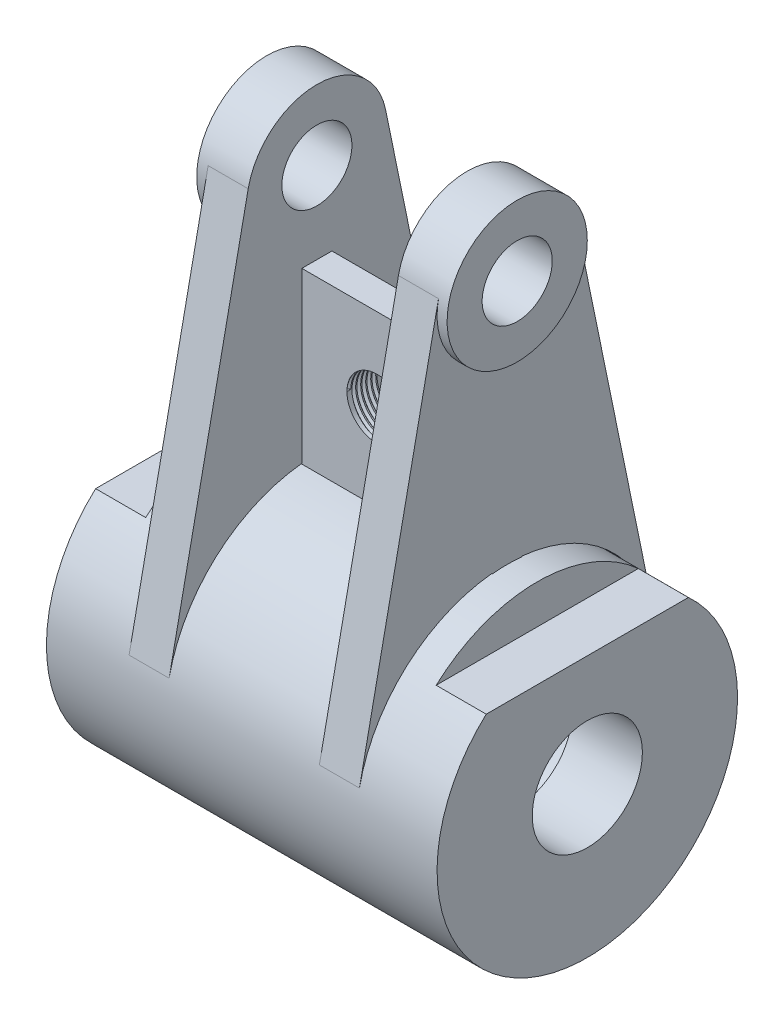
SolidWorks part; units mm, degrees
ref_plane "Front Plane" through (0, 0, 0) normal (0, 0, 1) x (1, 0, 0)
ref_plane "Top Plane" through (0, 0, 0) normal (0, 1, 0) x (1, 0, 0)
ref_plane "Right Plane" through (0, 0, 0) normal (1, 0, 0) x (0, 0, -1)
sketch "Sketch1" plane through (0, 0, 0) normal (1, 0, 0) x (0, 0, -1)
  circle A0 centre (0, 0) radius 30
  dimension "D1" = 60
extrude "Boss-Extrude1" add sketch "Sketch1" along normal mid plane 78
sketch "Sketch2" plane through (39, 0, 0) normal (1, 0, 0) x (0, 0, -1)
  line L0 (0, -30) -> (0, 22.1962)
  line L1 (-21.6282, 22.1962) -> (22.0652, 22.1962)
  circle A0 centre (0, 0) radius 30 construction
  circle A1 centre (0, 0) radius 30
  circle M3 centre (0, 0) radius 30
  dimension "D1" = 52.1962
extrude "Cut-Extrude1" cut sketch "Sketch2" against normal blind 10 contours L1 M3 region at (39, 25.3554, 0)
mirror "Mirror2" about plane through (0, 0, 0) normal (1, 0, 0) of "Cut-Extrude1"
sketch "Sketch3" plane through (0, 0, 0) normal (1, 0, 0) x (0, 0, -1)
  circle A0 centre (0, 0) radius 30
  circle A1 centre (0, 0) radius 18
  dimension "D1" = 36
extrude "Cut-Extrude2" cut sketch "Sketch3" against normal mid plane 50 contours A1
sketch "Sketch4" plane through (39, 0, 0) normal (1, 0, 0) x (0, 0, -1)
  circle A0 centre (0, 0) radius 11
  dimension "D1" = 22
extrude "Cut-Extrude3" cut sketch "Sketch4" against normal mid plane 188
sketch3d "3DSketch1" plane through (0, 0, 0) normal (0, 0, 1) x (1, 0, 0)
  dimension "D1" = 15
  dimension "D2" = 15
ref_plane "Plane3" through (15, 0, 0) normal (1, 0, 0) x (0, 0, -1)
ref_plane "Plane4" through (-15, 0, 0) normal (1, 0, 0) x (0, 0, -1)
sketch "Sketch6" plane through (-15, 0, 0) normal (1, 0, 0) x (0, 0, -1)
  line L0 (0, 0) -> (0, 80)
  line L1 (-13.7129, 82.8206) -> (-29.5004, 6.068)
  line L2 (13.7129, 82.8206) -> (29.5004, 6.068)
  line L3 (0, 80) -> (0, 63.7)
  line L4 (0, 63.7) -> (-3, 63.7)
  line L6 (-3, 63.7) -> (3, 63.7)
  line L7 (-3, 63.7) -> (-3, 26.2051)
  line L8 (-3, 26.2051) -> (3, 26.2051)
  line L9 (3, 63.7) -> (3, 26.2051)
  circle A0 centre (0, 0) radius 30.118
  circle A1 centre (0, 80) radius 7
  circle A2 centre (0, 80) radius 14
  dimension "D2" = 14
  dimension "D3" = 28
  dimension "D1" = 80
  dimension "D4" = 16.3
  dimension "D5" = 3
  dimension "D6" = 6
extrude "Boss-Extrude2" add sketch "Sketch6" against normal blind 10 contours A2 L0 L6 L9 A0 L2 | A2 L1 A0 L7 L4 L0 | A2 A1 | L7 L8 L9 L6 region at (-15, 45.6847, 13.1779) region at (-15, 45.6847, -13.1779) region at (-15, 71.404, 10.5441)
sketch "Sketch7" plane through (-25, 0, 0) normal (-1, 0, 0) x (0, 0, 1)
  line L4 (-3, 29.9682) -> (-3, 29.8496)
  line L5 (3, 29.8496) -> (3, 29.9682)
  line L6 (29.5004, 6.068) -> (13.7129, 82.8206)
  line L7 (-13.7129, 82.8206) -> (-29.5004, 6.068)
  line L8 (-3, 29.9682) -> (-3, 29.8496)
  line L9 (3, 29.8496) -> (3, 29.9682)
  line L10 (29.5004, 6.068) -> (13.7129, 82.8206)
  line L11 (-13.7129, 82.8206) -> (-29.5004, 6.068)
  circle A0 centre (0, 80) radius 14
  arc A5 (3, 29.8496) -> (-3, 29.8496) centre (0, 0) ccw
  arc A6 (29.5004, 6.068) -> (3, 29.9682) centre (0, 0) ccw
  arc A7 (13.7129, 82.8206) -> (-13.7129, 82.8206) centre (0, 80) ccw
  arc A8 (-3, 29.9682) -> (-29.5004, 6.068) centre (0, 0) ccw
  arc A9 (3, 29.8496) -> (-3, 29.8496) centre (0, 0) ccw
  arc A10 (29.5004, 6.068) -> (3, 29.9682) centre (0, 0) ccw
  arc A11 (13.7129, 82.8206) -> (-13.7129, 82.8206) centre (0, 80) ccw
  arc A12 (-3, 29.9682) -> (-29.5004, 6.068) centre (0, 0) ccw
  line M2 (-3, 29.9682) -> (-3, 29.8496)
  arc M3 (-3, 29.8496) -> (3, 29.8496) centre (0, 0) cw
  line M4 (3, 29.8496) -> (3, 29.9682)
  arc M5 (3, 29.9682) -> (29.5004, 6.068) centre (0, 0) cw
  line M6 (29.5004, 6.068) -> (13.7129, 82.8206)
  line M8 (-13.7129, 82.8206) -> (-29.5004, 6.068)
  arc M9 (-29.5004, 6.068) -> (-3, 29.9682) centre (0, 0) cw
  dimension "D1" = 0
extrude "Cut-Extrude4" cut sketch "Sketch7" against normal blind 2 contours A0 M8 M9 M2 M3 M4 M5 M6 region at (-25, 45.8082, 0)
mirror "Mirror3" about plane through (0, 0, 0) normal (1, 0, 0) of "Cut-Extrude4", "Boss-Extrude2"
extrude "Boss-Extrude3" add sketch "Sketch6<3>" along normal blind 32 contours L7 L8 L9 L6
sketch "Sketch6<3>" plane through (-15, 0, 0) normal (1, 0, 0) x (0, 0, -1) same geometry as "Sketch6"
sketch "Sketch8" plane through (0, 0, -3) normal (0, 0, -1) x (-1, 0, 0)
  line L0 (0, 33) -> (0, -33) construction
  circle A0 centre (0, 46.8994) radius 6
  point P0 (0, 46.8994)
  dimension "D1" = 12
extrude "Cut-Extrude5" cut sketch "Sketch8" against normal mid plane 83
sketch "Sketch16" plane through (0, 0, 0) normal (0, 1, 0) x (1, 0, 0)
  circle A0 centre (0, 0) radius 8
  dimension "D1" = 16
extrude "Cut-Extrude6" cut sketch "Sketch16" against normal blind 83
thread "Thread2" pitch 1 method cut profile "Thread Profile2" start angle 0, offset 0, length 10, pitch 1, diameter 12
ref_plane "Plane6" through (-6, 46.8994, 3) normal (0, -1, 0) x (-1, 0, 0)
sketch "Thread Profile2" plane through (-6, 46.8994, 3) normal (0, -1, 0) x (-1, 0, 0)
  line L0 (0, 0) -> (0, 1) construction
  line L1 (0, 0) -> (0.5413, 0.3125)
  line L2 (0.5413, 0.3125) -> (0.5413, 0.4375)
  line L3 (0.5413, 0.4375) -> (0, 0.75)
  line L4 (0.5413, 0.375) -> (0, 0.375) construction
  line L11 (0, 0) -> (0, 0.75)
  point P2 (0, 0)
  dimension "Pitch" = 1
  dimension "Profile_Angle" = 60
  dimension "Profile_Land" = 0.125
  dimension "Profile_Height" = 0.5413
